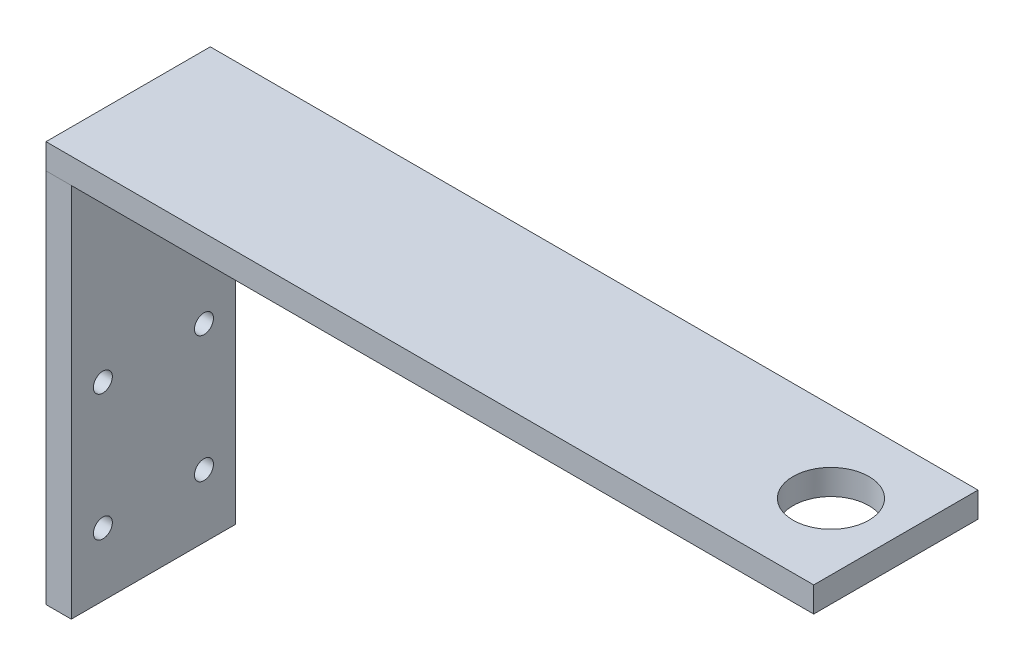
SolidWorks part; units mm, degrees
ref_plane "Front Plane" through (0, 0, 0) normal (0, 0, 1) x (1, 0, 0)
ref_plane "Top Plane" through (0, 0, 0) normal (0, 1, 0) x (1, 0, 0)
ref_plane "Right Plane" through (0, 0, 0) normal (1, 0, 0) x (0, 0, -1)
ref_plane "Plane1" through (0, 103.45, 0) normal (0, -1, 0) x (-1, 0, 0)
ref_axis "Axis1" through (75, 103.45, -75) along (0, 0, 1)
ref_axis "Axis2" through (75, 78.95, 0) along (0, -1, 0)
sketch "Sketch2" plane through (75, 0, 0) normal (-1, 0, 0) x (0, 0, 1)
  line L0 (-75, 103.45) -> (75, 103.45) construction
  line L1 (11, 105.1) -> (11, 45.916) construction
  line L7 (0, 78.95) -> (0, -7.95) construction
  line L8 (0, 99.45) -> (0, 25.2986) construction
  line L10 (-11, 105.05) -> (-11, 44.5284) construction
  line L11 (13, 103.45) -> (-13, 103.45)
  line L13 (13, 99.45) -> (-13, 99.45)
  line L14 (-13, 103.45) -> (-13, 99.45)
  line L15 (13, 103.45) -> (13, 99.45)
  point P0 (0, 103.45)
  point P5 (-11, 105.1)
  point P7 (11, 105.1)
  point P16 (-11, 105.05)
  point P17 (0, 65.35)
  point P23 (0, 103.45)
  dimension "D1" = 4
  dimension "D2" = 2
extrude "Boss-Extrude1" add sketch "Sketch2" against normal offset from surface (117.5 mm away) 2 offset beyond the face yes
ref_plane "Plane2" through (0, 99.45, 0) normal (0, -1, 0) x (-1, 0, 0)
sketch "Sketch4" plane through (0, 99.45, 0) normal (0, -1, 0) x (1, 0, 0)
  line L0 (185, -0.23) -> (179, -0.23) construction
  line L1 (176, -0.23) -> (188, -0.23) construction
  circle A0 centre (182, -0.23) radius 6
  point P0 (179, -0.23)
  point P1 (185, -0.23)
  dimension "D1" = 12
extrude "Cut-Extrude2" cut sketch "Sketch4" against normal up to next
sketch "Sketch5" plane through (0, 103.45, 0) normal (0, 1, 0) x (1, 0, 0)
  line L7 (192.5, 13) -> (75, 13) construction
  line L8 (75, 13) -> (71, 13)
  line L9 (75, 13) -> (75, -13)
  line L10 (75, -13) -> (71, -13)
  line L11 (71, 13) -> (71, -13)
  line L12 (75, 75) -> (75, -75) construction
  line L13 (192.5, -13) -> (75, -13) construction
  dimension "D1" = 4
extrude "Boss-Extrude2" add sketch "Sketch5" against normal offset from surface (63.45 mm away) 40
sketch "Sketch6" plane through (71, 0, 0) normal (-1, 0, 0) x (0, 0, 1)
  line L0 (-13, 45) -> (13, 45) construction
  line L2 (-13, 75) -> (13, 75) construction
  line L3 (-13, 75) -> (-13, 45) construction
  line L4 (-8, 70) -> (-8, 50) construction
  line L9 (8, 70) -> (8, 50) construction
  line L11 (-8, 70) -> (8, 70) construction
  line L12 (-8, 50) -> (8, 50) construction
  line L14 (-13, 40) -> (-13, 103.45) construction
  line L15 (13, 40) -> (13, 103.45) construction
  circle A0 centre (-8, 70) radius 1.5
  circle A1 centre (8, 70) radius 1.5
  circle A2 centre (-8, 50) radius 1.5
  circle A3 centre (8, 50) radius 1.5
  dimension "D5" = 3
  dimension "D1" = 5
  dimension "D2" = 5
  dimension "D3" = 5
  dimension "D4" = 5
extrude "Cut-Extrude3" cut sketch "Sketch6" against normal up to next
ref_plane "Plane3" through (0, 99.45, 0) normal (0, -1, 0) x (-1, 0, 0)
split "Split1" trim tools "Plane3" bodies to split 105 resulting bodies 106 107
